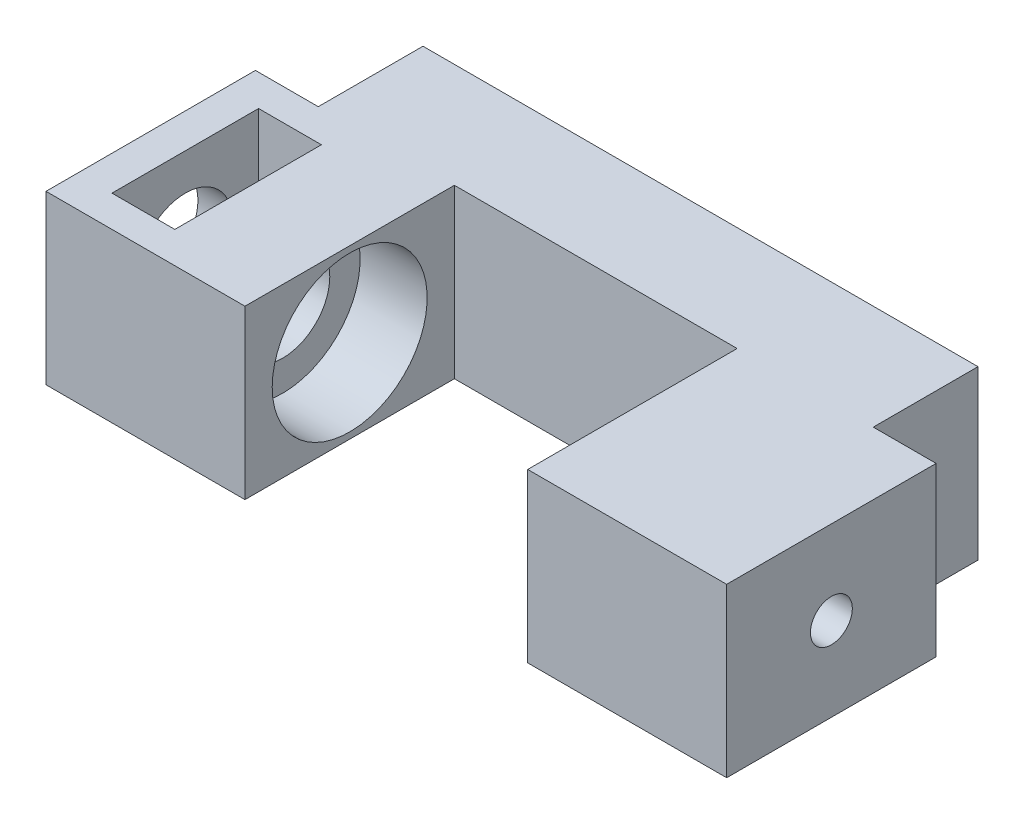
SolidWorks part; units mm, degrees
material "ABS"
ref_plane "Plan de face" through (0, 0, 0) normal (0, 0, 1) x (1, 0, 0)
ref_plane "Plan de dessus" through (0, 0, 0) normal (0, 1, 0) x (1, 0, 0)
ref_plane "Plan de droite" through (0, 0, 0) normal (1, 0, 0) x (0, 0, -1)
sketch "Length" plane through (0, 0, 0) normal (0, 1, 0) x (1, 0, 0)
  line L0 (0, 0) -> (0, 117) construction
  dimension "D1" = 117
sketch "Length2" plane through (0, 0, 0) normal (1, 0, 0) x (0, 0, -1)
  line L0 (100, 0) -> (100, 40) construction
  line L1 (0, 0) -> (117, 0) construction
  dimension "D1" = 40
  dimension "D2" = 100
sketch3d "TopPlane"
sketch "Esquisse17" plane through (0, 40, 0) normal (0, -1, 0) x (-1, 0, 0)
  line L0 (13.25, 105) -> (13.25, 95)
  line L1 (13.25, 95) -> (6.75, 95)
  line L2 (6.75, 95) -> (6.75, 105)
  line L3 (6.75, 105) -> (-6.75, 105)
  line L4 (-6.75, 105) -> (-6.75, 95)
  line L5 (-6.75, 95) -> (-13.25, 95)
  line L6 (-13.25, 95) -> (-13.25, 105)
  line L7 (-13.25, 105) -> (-13.25, 110)
  line L8 (-13.25, 110) -> (13.25, 110)
  line L9 (13.25, 110) -> (13.25, 105)
  line L10 (0, 0) -> (0, 117) construction
  line L11 (0, 100) -> (13.25, 100) construction
  line L12 (13.25, 105) -> (6.75, 105) construction
  line L13 (-6.75, 105) -> (-13.25, 105) construction
  line L14 (-10, 105) -> (-10, 95) construction
  line L15 (10, 105) -> (10, 95) construction
  point P12 (0, 105)
  dimension "D1" = 6.5
  dimension "D2" = 5
  dimension "D3" = 20
  dimension "D4" = 10
  dimension "D5" = 5
extrude "Shape" add sketch "Esquisse17" along normal blind 4 and the other way blind 4 separate body
sketch "Esquisse19" plane through (-13.25, 0, 0) normal (-1, 0, 0) x (0, 0, 1)
  circle A0 centre (-100, 40) radius 2.25
  dimension "D1" = 4.5
extrude "HoleAxe_motor" cut sketch "Esquisse19" against normal blind 13
sketch "Esquisse20" plane through (6.75, 0, 0) normal (-1, 0, 0) x (0, 0, 1)
  circle A0 centre (-100, 40) radius 3.7
  dimension "D1" = 7.4
extrude "HoleBearing_motor" cut sketch "Esquisse20" against normal blind 3.2
mirror "Symétrie3" about plane through (0, 0, 0) normal (1, 0, 0) of "HoleBearing_motor"
sketch "Esquisse21" plane through (9.95, 0, 0) normal (-1, 0, 0) x (0, 0, 1)
  circle A0 centre (-100, 40) radius 2.2
  circle A1 centre (-100, 40) radius 3.7 construction
  dimension "D1" = 1.5
extrude "entretoiseBearing_motor" cut sketch "Esquisse21" against normal blind 1
sketch "Esquisse22" plane through (-13.25, 0, 0) normal (-1, 0, 0) x (0, 0, 1)
  line L0 (-95, 36) -> (-110, 36) construction
  line L1 (-95, 44) -> (-105, 44)
  line L2 (-95, 44) -> (-95, 36)
  line L3 (-95, 36) -> (-105, 36)
  line L4 (-105, 44) -> (-105, 36)
  circle A0 centre (-100, 40) radius 2.25
  circle A1 centre (-100, 40) radius 2.25 construction
extrude "Ext_motor" add sketch "Esquisse22" along normal blind 3
sketch "Esquisse23" plane through (0, 44, 0) normal (0, 1, 0) x (1, 0, 0)
  line L0 (-13.25, 105) -> (-6.75, 105) construction
  line L1 (-9.95, 95) -> (-9.95, 105) construction
  line L2 (-6.75, 95) -> (-16.25, 95) construction
  line L3 (-9.95, 100) -> (-16.25, 100) construction
  line L4 (-16.25, 95) -> (-16.25, 105) construction
  line L5 (-9.95, 96.3) -> (-9.95, 103.7) construction
  line L7 (-14.6, 96.5) -> (-11.6, 96.5)
  line L8 (-14.6, 96.5) -> (-14.6, 103.5)
  line L9 (-14.6, 103.5) -> (-11.6, 103.5)
  line L10 (-11.6, 96.5) -> (-11.6, 103.5)
  line L11 (-14.6, 96.5) -> (-11.6, 103.5) construction
  line L12 (-14.6, 103.5) -> (-11.6, 96.5) construction
  point P14 (-13.1, 100)
  dimension "D1" = 3
  dimension "D2" = 7
extrude "HoleScrewLess_motor" cut sketch "Esquisse23" against normal blind 10
sketch "Esquisse24" plane through (13.25, 0, 0) normal (1, 0, 0) x (0, 0, -1)
  line L5 (105, 44) -> (105, 36) construction
  line L6 (105, 36) -> (95, 36)
  line L7 (105, 36) -> (105, 44)
  line L8 (105, 44) -> (95, 44)
  line L9 (95, 36) -> (95, 44)
  line L10 (105, 36) -> (95, 44) construction
  line L11 (105, 44) -> (95, 36) construction
  point P0 (100, 40)
extrude "Boss.-Extru.1" add sketch "Esquisse24" along normal blind 3
sketch "Esquisse25" plane through (10.95, 0, 0) normal (-1, 0, 0) x (0, 0, 1)
  circle A0 centre (-100, 40) radius 1
  dimension "D1" = 2
extrude "Remove helper" cut sketch "Esquisse25" against normal blind 10
equation "\"entretoiseBearing\"= 1.5mm"
equation "\"length_tibia\"= 206mm"
equation "\"length_femur\"= 117mm"
equation "\"length_coxa\"= 27mm"
equation "\"height\"= 40mm"
equation "\"width\"= 100mm"
equation "\"lever\"= 40mm"
equation "\"depthMagnet\"= 1mm"
equation "\"D1@Length\"=\"length_femur\""
equation "\"D1@Length2\"=\"height\""
equation "\"D1@Esquisse19\"=\"entretoiseBearing\"+3"
equation "\"D1@Esquisse21\"=\"entretoiseBearing\""
equation "\"D2@Length2\"=\"width\""
equation "\"D1@Ref\" = \"length_femur\""
equation "\"errorFlat\"= 0.20mm"
equation "\"errorCircle\"= 0.40mm"
equation "\"cuticule\"=1.5mm"
equation "\"D1@Esquisse20\"=\"errorCircle\"+7"
equation "\"D1@HoleBearing_motor\"=\"errorFlat\"+3"
